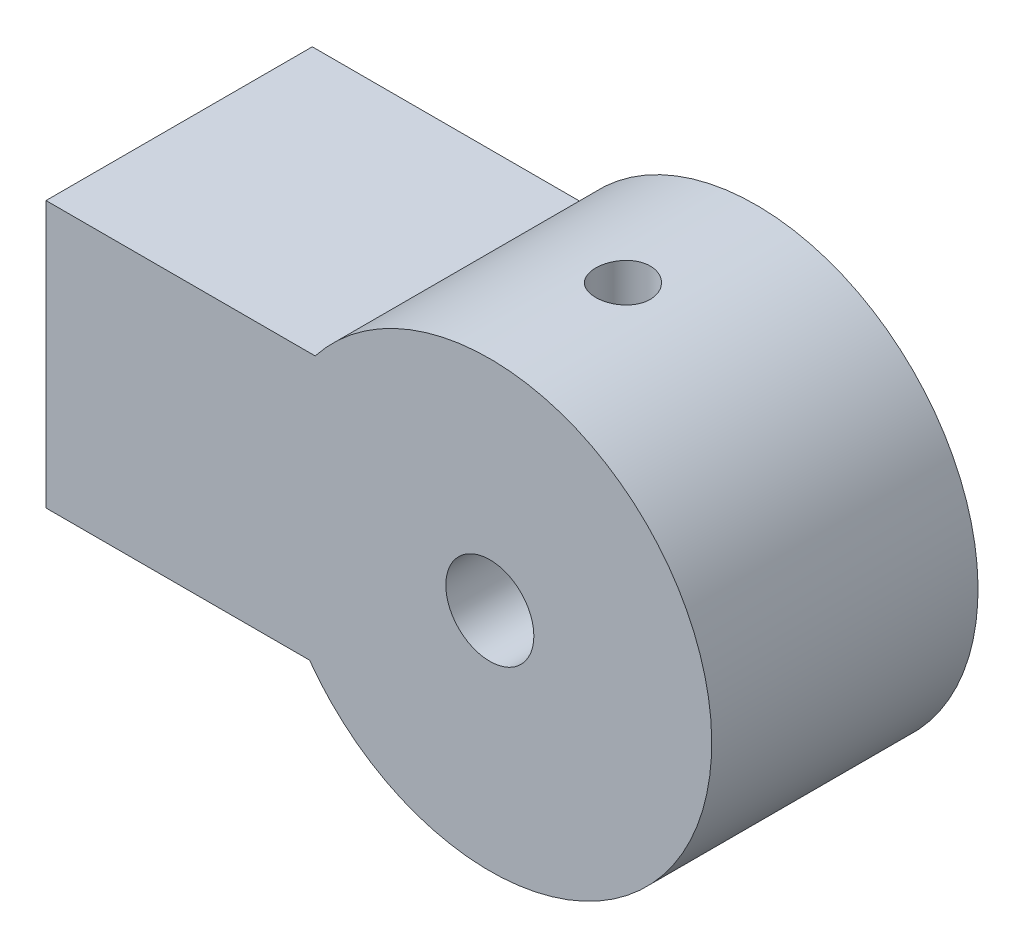
SolidWorks part; units mm, degrees
material "PLA"
ref_plane "Front Plane" through (0, 0, 0) normal (0, 0, 1) x (1, 0, 0)
ref_plane "Top Plane" through (0, 0, 0) normal (0, 1, 0) x (1, 0, 0)
ref_plane "Right Plane" through (0, 0, 0) normal (1, 0, 0) x (0, 0, -1)
sketch "Sketch1" plane through (0, 0, 0) normal (0, 0, 1) x (1, 0, 0)
  line L0 (0, 0) -> (0, 19.05)
  line L1 (0, 19.05) -> (31.75, 19.05)
  line L2 (31.75, 19.05) -> (31.75, 0)
  line L3 (31.75, 0) -> (0, 0)
  circle A0 centre (31.75, 9.525) radius 9.525
  circle A1 centre (31.75, 9.525) radius 3.15
  circle A2 centre (31.75, 9.256) radius 15.875
  dimension "D3" = 6.3
  dimension "D4" = 31.75
  dimension "D1" = 31.75
  dimension "D2" = 19.05
extrude "Boss-Extrude1" add sketch "Sketch1" along normal blind 19.05 contours A1 L2 A0 | A1 L2 A0 | A0 L1 L0 L3 | A2 L1 L0 L3 | L3 A2 L1 A0 region at (8.4709, 9.5595, 0) region at (20.8262, 9.4461, 0) region at (25.3013, -0.4285, 0) region at (27.3752, 9.525, 0) region at (36.1248, 9.525, 0)
ref_plane "Plane1" through (0, 25.4, 0) normal (0, 1, 0) x (1, 0, 0)
sketch "Sketch3" plane through (0, 19.05, 0) normal (0, 1, 0) x (1, 0, 0)
  line L4 (19.2562, 0) -> (0, 0)
  line L5 (0, 0) -> (0, -19.05)
  line L6 (0, -19.05) -> (19.2562, -19.05)
  line L7 (19.2562, -19.05) -> (19.2562, 0)
  line L8 (19.2562, 0) -> (0, 0)
  line L9 (0, 0) -> (0, -19.05)
  line L10 (0, -19.05) -> (19.2562, -19.05)
  line L11 (19.2562, -19.05) -> (19.2562, 0)
  line L12 (18.8527, -19.05) -> (47.625, -19.05) construction
  line L13 (18.8527, -19.05) -> (47.625, -19.05)
  line L14 (31.75, -17.4979) -> (31.75, -1.3096) construction
  line L15 (19.2562, -9.525) -> (31.75, -9.525) construction
  line L16 (28.6, -19.05) -> (34.9, -19.05) construction
  line L17 (28.6, -19.05) -> (34.9, -19.05)
  line L18 (28.6, -17.4979) -> (34.9, -17.4979) construction
  circle A0 centre (31.75, -9.525) radius 1.95
  dimension "D2" = 3.9
  dimension "D1" = 0
extrude "Cut-Extrude2" cut sketch "Sketch3" against normal up to surface (12.725 mm away) from surface contours A0 region at (31.75, 19.05, 9.525) up to face at (34.9, 9.525, 19.05) starting at plane "Plane1"
